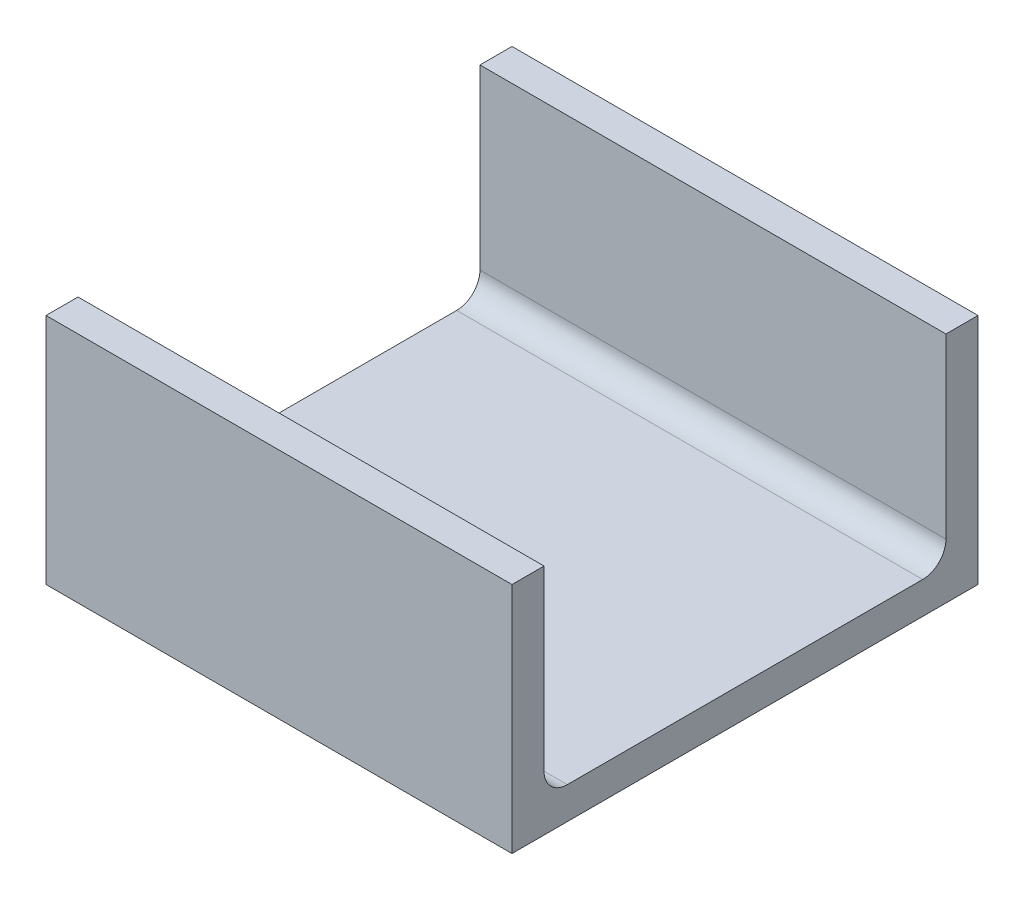
SolidWorks part; units mm, degrees
ref_plane "Front Plane" through (0, 0, 0) normal (0, 0, 1) x (1, 0, 0)
ref_plane "Top Plane" through (0, 0, 0) normal (0, 1, 0) x (1, 0, 0)
ref_plane "Right Plane" through (0, 0, 0) normal (1, 0, 0) x (0, 0, -1)
sketch "Sketch1" plane through (0, 0, 0) normal (1, 0, 0) x (0, 0, -1)
  line L0 (-21.9075, 9.2075) -> (21.9075, 9.2075)
  line L1 (-25.4, -12.7) -> (25.4, -12.7)
  line L2 (-25.4, -12.7) -> (-25.4, 12.7)
  line L3 (-25.4, 12.7) -> (25.4, 12.7)
  line L4 (25.4, -12.7) -> (25.4, 12.7)
  line L5 (-25.4, -12.7) -> (25.4, 12.7) construction
  line L6 (-25.4, 12.7) -> (25.4, -12.7) construction
  line L7 (21.9075, -6.6675) -> (21.9075, 9.2075)
  line L8 (-19.3675, -9.2075) -> (19.3675, -9.2075)
  line L9 (-21.9075, -6.6675) -> (-21.9075, 9.2075)
  line L10 (-21.9075, 9.2075) -> (-21.9075, 12.7)
  line L11 (21.9075, 9.2075) -> (21.9075, 12.7)
  line L12 (21.9075, -9.2075) -> (21.9075, 9.2075) construction
  line L13 (-21.9075, -9.2075) -> (21.9075, -9.2075) construction
  line L14 (-21.9075, -9.2075) -> (-21.9075, 9.2075) construction
  arc A0 (21.9075, -6.6675) -> (19.3675, -9.2075) centre (19.3675, -6.6675) cw
  arc A1 (-19.3675, -9.2075) -> (-21.9075, -6.6675) centre (-19.3675, -6.6675) cw
  point P0 (0, 0)
  dimension "D4" = 2.54
  dimension "D1" = 25.4
  dimension "D2" = 50.8
  dimension "D3" = 3.4925
extrude "Boss-Extrude1" add sketch "Sketch1" along normal blind 50.8 contours L8 A1 L9 L10 L3 L2 L1 L4 L11 L7 A0 region at (0, 1.27, 22.4755)
